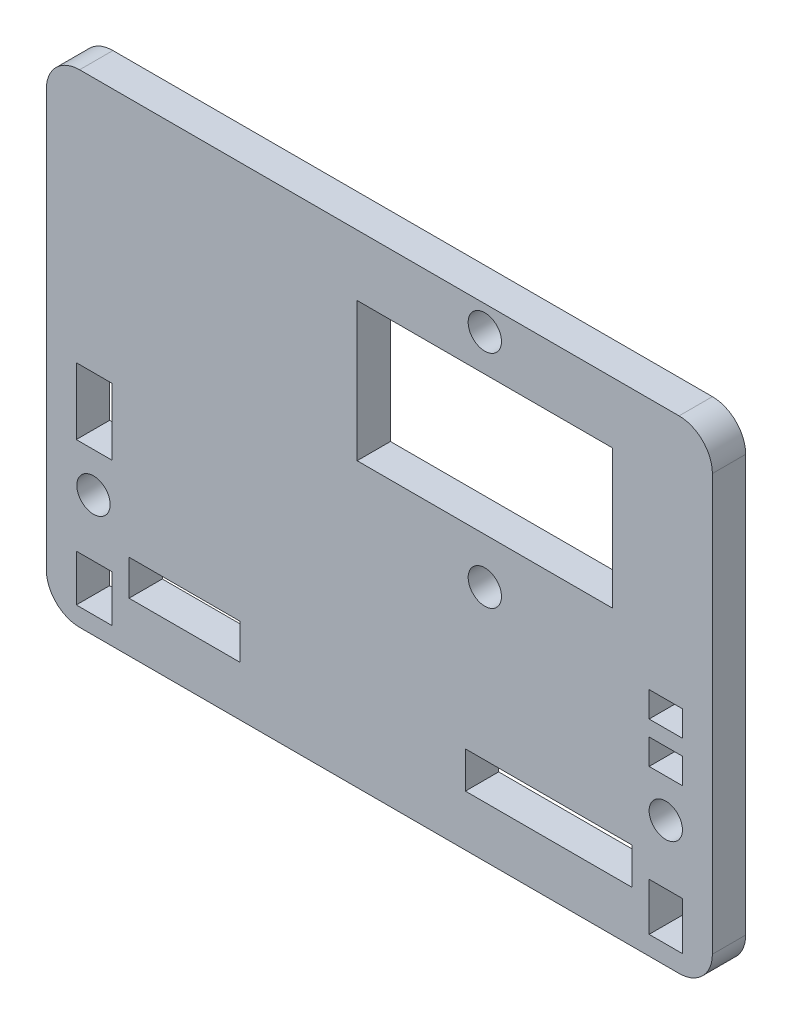
SolidWorks part; units mm, degrees
ref_plane "Plan de face" through (0, 0, 0) normal (0, 0, 1) x (1, 0, 0)
ref_plane "Plan de dessus" through (0, 0, 0) normal (0, 1, 0) x (1, 0, 0)
ref_plane "Plan de droite" through (0, 0, 0) normal (1, 0, 0) x (0, 0, -1)
sketch "Esquisse1" plane through (0, 0, 0) normal (0, 0, 1) x (1, 0, 0)
  line L0 (-829.3382, 1697.689) -> (-769.3382, 1697.689) construction
  line L1 (-785.6657, 1690.2775) -> (-785.6657, 1706.0775) construction
  line L2 (-822.1657, 1708.2775) -> (-768.1657, 1708.2775)
  line L3 (-825.1657, 1705.2775) -> (-825.1657, 1667.7775)
  line L4 (-822.1657, 1664.7775) -> (-768.1657, 1664.7775)
  line L5 (-765.1657, 1705.2775) -> (-765.1657, 1667.7775)
  line L6 (-825.1657, 1708.2775) -> (-765.1657, 1664.7775) construction
  line L7 (-825.1657, 1664.7775) -> (-765.1657, 1708.2775) construction
  line L8 (-797.1657, 1702.7775) -> (-774.1657, 1702.7775)
  line L9 (-797.1657, 1702.7775) -> (-797.1657, 1690.2775)
  line L10 (-797.1657, 1690.2775) -> (-774.1657, 1690.2775)
  line L11 (-774.1657, 1702.7775) -> (-774.1657, 1690.2775)
  line L12 (-797.1657, 1696.5275) -> (-774.1657, 1696.5275) construction
  line L13 (-785.6657, 1690.2775) -> (-785.6657, 1683.2333) construction
  line L15 (-822.4657, 1685.2775) -> (-819.2657, 1685.2775)
  line L16 (-822.4657, 1685.2775) -> (-822.4657, 1679.2775)
  line L17 (-822.4657, 1679.2775) -> (-819.2657, 1679.2775)
  line L18 (-819.2657, 1685.2775) -> (-819.2657, 1679.2775)
  line L19 (-822.4657, 1670.5775) -> (-819.2657, 1670.5775)
  line L20 (-822.4657, 1670.5775) -> (-822.4657, 1666.3775)
  line L21 (-822.4657, 1666.3775) -> (-819.2657, 1666.3775)
  line L22 (-819.2657, 1670.5775) -> (-819.2657, 1666.3775)
  line L23 (-817.7157, 1672.4775) -> (-807.7157, 1672.4775)
  line L24 (-817.7157, 1672.4775) -> (-817.7157, 1669.2775)
  line L25 (-817.7157, 1669.2775) -> (-807.7157, 1669.2775)
  line L26 (-807.7157, 1672.4775) -> (-807.7157, 1669.2775)
  line L27 (-787.4157, 1672.6775) -> (-772.4157, 1672.6775)
  line L28 (-787.4157, 1672.6775) -> (-787.4157, 1669.3775)
  line L29 (-787.4157, 1669.3775) -> (-772.4157, 1669.3775)
  line L30 (-772.4157, 1672.6775) -> (-772.4157, 1669.3775)
  line L31 (-770.8657, 1670.7775) -> (-767.8657, 1670.7775)
  line L32 (-770.8657, 1670.7775) -> (-770.8657, 1666.4775)
  line L33 (-770.8657, 1666.4775) -> (-767.8657, 1666.4775)
  line L34 (-767.8657, 1670.7775) -> (-767.8657, 1666.4775)
  line L35 (-770.8657, 1681.8775) -> (-767.8657, 1681.8775)
  line L36 (-770.8657, 1681.8775) -> (-770.8657, 1679.5775)
  line L37 (-770.8657, 1679.5775) -> (-767.8657, 1679.5775)
  line L38 (-767.8657, 1681.8775) -> (-767.8657, 1679.5775)
  line L39 (-770.8657, 1685.5775) -> (-767.8657, 1685.5775)
  line L40 (-770.8657, 1685.5775) -> (-770.8657, 1683.2775)
  line L41 (-770.8657, 1683.2775) -> (-767.8657, 1683.2775)
  line L42 (-767.8657, 1685.5775) -> (-767.8657, 1683.2775)
  arc A0 (-768.1657, 1664.7775) -> (-765.1657, 1667.7775) centre (-768.1657, 1667.7775) ccw
  arc A1 (-825.1657, 1667.7775) -> (-822.1657, 1664.7775) centre (-822.1657, 1667.7775) ccw
  arc A2 (-822.1657, 1708.2775) -> (-825.1657, 1705.2775) centre (-822.1657, 1705.2775) ccw
  arc A3 (-768.1657, 1708.2775) -> (-765.1657, 1705.2775) centre (-768.1657, 1705.2775) cw
  circle A4 centre (-785.6657, 1706.0775) radius 1.5
  circle A5 centre (-785.6657, 1686.1775) radius 1.5
  circle A6 centre (-820.9157, 1675.7275) radius 1.5
  circle A7 centre (-769.3657, 1676.1275) radius 1.5
  point P3 (-795.1657, 1686.5275)
  point P32 (-785.6657, 1698.1775)
  dimension "D9" = 3
  dimension "D10" = 3
  dimension "D12" = 3
  dimension "D16" = 3
  dimension "D17" = 3
  dimension "D49" = 2.75
  dimension "D1" = 60
  dimension "D2" = 60
  dimension "D3" = 43.5
  dimension "D4" = 23
  dimension "D5" = 23
  dimension "D6" = 12.5
  dimension "D7" = 9
  dimension "D8" = 5.5
  dimension "D11" = 2.6
  dimension "D13" = 1.8
  dimension "D14" = 785.6657
  dimension "D15" = 1698.1775
  dimension "D18" = 3
  dimension "D19" = 3
  dimension "D20" = 2.3
  dimension "D21" = 2.3
  dimension "D22" = 2.7
  dimension "D23" = 2.7
  dimension "D24" = 14.8
  dimension "D25" = 1.4
  dimension "D26" = 4.3
  dimension "D27" = 3
  dimension "D28" = 2.7
  dimension "D29" = 1.7
  dimension "D30" = 2.7
  dimension "D31" = 1.95
  dimension "D32" = 3.3
  dimension "D33" = 15
  dimension "D34" = 7.25
  dimension "D35" = 4.6
  dimension "D36" = 10
  dimension "D37" = 3.2
  dimension "D38" = 4.5
  dimension "D39" = 7.45
  dimension "D40" = 4.2
  dimension "D41" = 3.2
  dimension "D42" = 1.6
  dimension "D43" = 2.7
  dimension "D44" = 6
  dimension "D45" = 3.2
  dimension "D46" = 2.7
  dimension "D47" = 8.7
  dimension "D48" = 3.65
base flange "Tôle de base pliée1" sketch "Esquisse1" thickness 3 reverse thickness direction no parameters "D1"=1.5
sketch "Lignes de pliage1" [suppressed] plane through (0, 0, 0) normal (0, 1, 0) x (1, 0, 0)
sketch "Cube de visualisation1" [suppressed] plane through (0, 0, 0) normal (0, 1, 0) x (1, 0, 0)
sheet metal parameters "Tôlerie1" thickness 3 parameters "D1"=1.5
flat pattern "Etat déplié1" [suppressed]
sketch "Lignes de pliage2" plane through (0, 0, 0) normal (0, 1, 0) x (1, 0, 0)
sketch3d "Cube de visualisation2" [suppressed]
  line L0 (-57, 40.5, 0) -> (3, 40.5, 0) construction
  line L1 (-57, -3, 0) -> (3, -3, 0) construction
  line L2 (-57, 40.5, 0) -> (-57, -3, 0) construction
  line L3 (3, 40.5, 0) -> (3, -3, 0) construction
